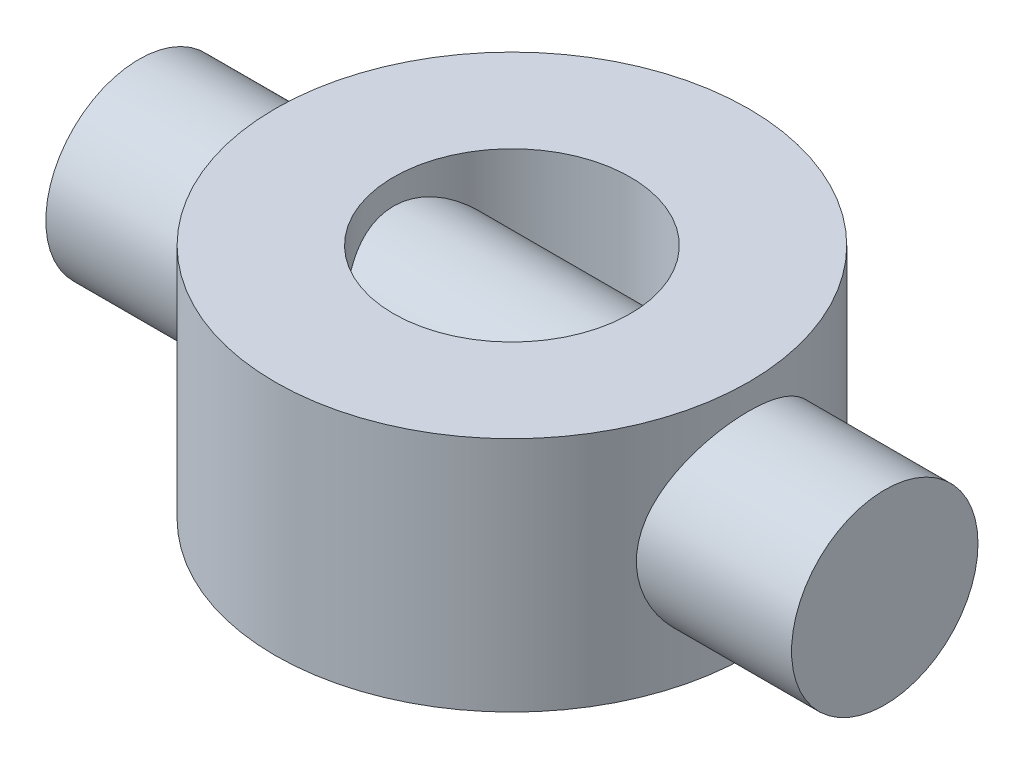
SolidWorks part; units mm, degrees
ref_plane "Front Plane" through (0, 0, 0) normal (0, 0, 1) x (1, 0, 0)
ref_plane "Top Plane" through (0, 0, 0) normal (0, 1, 0) x (1, 0, 0)
ref_plane "Right Plane" through (0, 0, 0) normal (1, 0, 0) x (0, 0, -1)
sketch "Sketch1" plane through (0, 0, 0) normal (0, 1, 0) x (1, 0, 0)
  circle A0 centre (0, 0) radius 12.7
  circle A1 centre (0, 0) radius 25.4
  dimension "D1" = 50.8
sketch "Sketch2" plane through (0, 0, 0) normal (1, 0, 0) x (0, 0, -1)
  line L0 (25.4, 0) -> (-25.4, 0) construction
  circle A0 centre (0, 0) radius 10
extrude "Boss-Extrude1" add sketch "Sketch2" along normal blind 40 and the other way blind 40
extrude "Boss-Extrude2" add sketch "Sketch1" along normal blind 12.7 and the other way blind 12.7
equation "\"toothBaseWidth\"=0.01"
equation "\"toothEndWidth\"=0.0075"
equation "\"toothLength\"=0.0075"
equation "\"holeWidth\" = 0.009"
equation "\"motorHolderToothSeparation\" = 0.01"
equation "\"magnetHolderToothSeparation\" = 0.02"
equation "\"magnetWidth\" = 0.0127"
equation "\"quarterInch\" = 0.00635"
equation "\"coilThickness\" = 0.0254"
equation "\"coilOuterDiameter\" = 0.0508"
equation "\"D1@Sketch1\"= \"coilOuterDiameter\""
equation "\"D1@Boss-Extrude2\"= \"coilThickness\"/2"
equation "\"D2@Boss-Extrude2\"= \"coilThickness\"/2"
